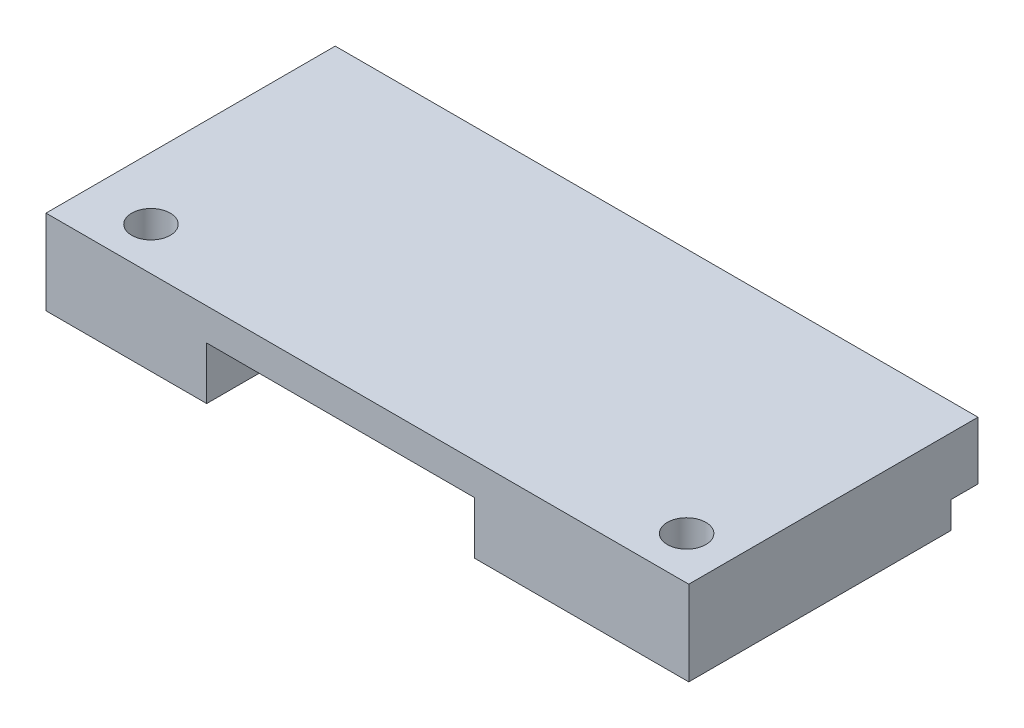
SolidWorks part; units mm, degrees
ref_plane "Płaszczyzna przednia" through (0, 0, 0) normal (0, 0, 1) x (1, 0, 0)
ref_plane "Płaszczyzna górna" through (0, 0, 0) normal (0, 1, 0) x (1, 0, 0)
ref_plane "Płaszczyzna prawa" through (0, 0, 0) normal (1, 0, 0) x (0, 0, -1)
sketch "Sketch1" plane through (0, 0, 0) normal (0, 1, 0) x (1, 0, 0)
  line L1 (-30, -1.25) -> (30, -1.25)
  line L2 (-30, -1.25) -> (-30, 1.25)
  line L3 (-30, 1.25) -> (30, 1.25)
  line L4 (30, -1.25) -> (30, 1.25)
  line L5 (-30, -1.25) -> (30, 1.25) construction
  line L6 (-30, 1.25) -> (30, -1.25) construction
  point P0 (0, 0)
  dimension "D1" = 2.5
  dimension "D2" = 60
extrude "Boss-Extrude1" add sketch "Sketch1" along normal blind 2.5
sketch "Sketch2" plane through (0, 2.5, 0) normal (0, 1, 0) x (1, 0, 0)
  line L0 (30, -1.25) -> (30, 1.25) construction
  line L1 (-30, -1.25) -> (30, -1.25)
  line L2 (-30, -1.25) -> (-30, 3.75)
  line L3 (-30, 3.75) -> (30, 3.75)
  line L4 (30, -1.25) -> (30, 3.75)
  line L9 (30, 1.25) -> (-30, 1.25) construction
  dimension "D1" = 2.5
extrude "Boss-Extrude2" add sketch "Sketch2" along normal blind 3
sketch "Sketch5" plane through (0, 0, 1.25) normal (0, 0, 1) x (1, 0, 0)
  line L4 (-30, 0) -> (30, 0)
  line L5 (30, 0) -> (30, 5.5)
  line L6 (30, 5.5) -> (-30, 5.5)
  line L7 (-30, 5.5) -> (-30, 0)
  line L8 (-30, 0) -> (30, 0)
  line L9 (30, 0) -> (30, 5.5)
  line L10 (30, 5.5) -> (-30, 5.5)
  line L11 (-30, 5.5) -> (-30, 0)
  dimension "D1" = 0
extrude "Boss-Extrude4" add sketch "Sketch5" along normal blind 22
sketch "Sketch6" plane through (0, 5.5, 0) normal (0, 1, 0) x (1, 0, 0)
  line L4 (-30, 3.75) -> (-30, -23.25)
  line L5 (-30, -23.25) -> (30, -23.25)
  line L6 (30, -23.25) -> (30, 3.75)
  line L7 (30, 3.75) -> (-30, 3.75)
  line L8 (-30, 3.75) -> (-30, -23.25)
  line L9 (-30, -23.25) -> (30, -23.25)
  line L10 (30, -23.25) -> (30, 3.75)
  line L11 (30, 3.75) -> (-30, 3.75)
  dimension "D1" = 0
extrude "Boss-Extrude5" add sketch "Sketch6" along normal blind 2.4
hole_wizard "Ø3.6 (3.6) Diameter Hole1" positions "Sketch7" profile "Sketch8" hole size "Ø3.6" standard "DIN" end condition through all
sketch "Sketch7" plane through (0, 7.9, 0) normal (0, 1, 0) x (1, 0, 0)
  line L1 (30, -23.25) -> (30, 3.75) construction
  line L2 (-30, -23.25) -> (30, -23.25) construction
  line L3 (25.8, -19.25) -> (-24.2, -19.25)
  point P0 (-24.2, -19.25)
  point P2 (25.8, -19.25)
  dimension "D1" = 50
  dimension "D2" = 4
  dimension "D3" = 4.2
sketch "Sketch8" plane through (-24.2, 7.9, 19.25) normal (1, 0, 0) x (0, 0, 1)
  line L0 (0, 0) -> (0, 7.9)
  line L1 (0, 7.9) -> (1.8, 7.9)
  line L2 (1.8, 7.9) -> (1.8, 0)
  line L5 (1.8, 0) -> (0, 0)
  line L11 (0, -6.35) -> (0, 107.95) construction
  dimension "Thru Hole Dia." = 3.6
  dimension "Thru Hole Depth" = 7.9
sketch "Sketch9" plane through (0, 0, -3.75) normal (0, 0, -1) x (-1, 0, 0)
  line L1 (-10, 4.9) -> (15, 4.9)
  line L2 (-10, 4.9) -> (-10, -4.7096)
  line L3 (-10, -4.7096) -> (15, -4.7096)
  line L4 (15, 4.9) -> (15, -4.7096)
  line L5 (30, 7.9) -> (30, 2.5) construction
  line L7 (-30, 7.9) -> (30, 7.9) construction
  dimension "D1" = 25
  dimension "D2" = 15
  dimension "D3" = 3
extrude "Cut-Extrude1" cut sketch "Sketch9" against normal through all
